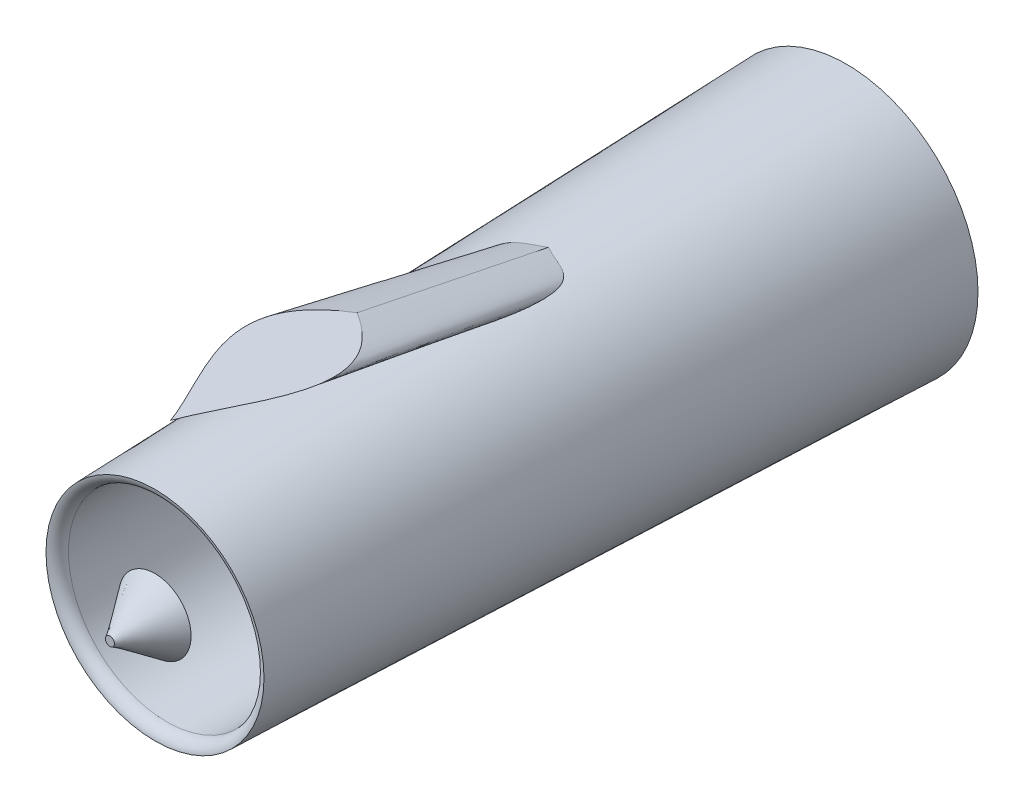
SolidWorks part; units mm, degrees
ref_plane "Front Plane" through (0, 0, 0) normal (0, 0, 1) x (1, 0, 0)
ref_plane "Top Plane" through (0, 0, 0) normal (0, 1, 0) x (1, 0, 0)
ref_plane "Right Plane" through (0, 0, 0) normal (1, 0, 0) x (0, 0, -1)
sketch "Sketch2" plane through (0, 0, 0) normal (0, 1, 0) x (1, 0, 0)
  line L0 (0, -6122.228) -> (0, 2040.7427)
  line L1 (0, 0) -> (-18096.1342, 0) construction
  line L2 (0, 0) -> (-21640.8, -16307.5125) construction
  line L3 (-21640.8, -18450.2946) -> (-21640.8, -15593.2518)
  line L4 (-21640.8, -15593.2518) -> (0, 2040.7427)
  line L5 (-21640.8, -18450.2946) -> (0, -6122.228)
  line L6 (-9083.802, -5361.1886) -> (-9083.802, -6845.1358) construction
  line L7 (-9083.802, -6845.1358) -> (-9083.802, -11296.9774) construction
  line L8 (-9083.802, -6845.1358) -> (0, -6845.1358) construction
  line L9 (0, 408.1485) -> (-18440.4, -13713.752)
  line L10 (0, -35661.6) -> (-7316.724, -42249.6079) construction
  line L11 (0, -35661.6) -> (-8167.6786, -35661.6) construction
  line L12 (0, -34539.0879) -> (0, -39029.1363)
  line L13 (-7316.724, -43428.2455) -> (-7316.724, -41856.7287)
  line L14 (-7316.724, -41856.7287) -> (0, -34539.0879)
  line L15 (0, -39029.1363) -> (-7316.724, -43428.2455)
  line L16 (-2544.3607, -37083.7674) -> (-2544.3607, -37952.5526) construction
  line L17 (-2544.3607, -37952.5526) -> (-2544.3607, -40558.9084) construction
  line L18 (-2544.3607, -37952.5526) -> (0, -37952.5526) construction
  line L19 (-18440.4, -13713.752) -> (-18440.4, -15898.787)
  line L20 (-18440.4, -15898.787) -> (0, -4489.6339)
  line L21 (0, 408.1485) -> (0, -4489.6339) construction
  line L22 (0, -4489.6339) -> (0, 408.1485) construction
  line L23 (0, 408.1485) -> (0, -2040.7427) construction
  line L24 (0, 408.1485) -> (0, -4489.6339) construction
  line L25 (0, -2040.7427) -> (-18440.4, -14806.2695) construction
  line L26 (0, 408.1485) -> (-21640.8, -16164.6603) construction
  line L27 (-6975.7046, -4933.9377) -> (-6975.7046, -6869.7347) construction
  line L28 (-6975.7046, -6869.7347) -> (-6975.7046, -8805.5317) construction
  line L29 (-6975.7046, -6869.7347) -> (0, -6869.7347) construction
  dimension "Wing Sweep" = 37
  dimension "Half Span" = 21640.8
  dimension "Wing Root" = 8162.9707
  dimension "D4" = 2040.7427
  dimension "Wing Tip" = 2857.0428
  dimension "D6" = 714.2607
  dimension "Wing YBar" = 9083.802
  dimension "Tail Sweep" = 42
  dimension "Tail Root" = 4490.0484
  dimension "D10" = 1122.5121
  dimension "Tail Tip" = 1571.5168
  dimension "D12" = 392.8792
  dimension "D13" = 7316.724
  dimension "Tail Ybar" = 2544.3607
  dimension "First Spar" = 1632.5941
  dimension "Second Spar" = 6530.3766
  dimension "Fuel Tip" = 2185.035
  dimension "Tip Spar" = 571.4086
  dimension "Fuel Ybar" = 6975.7046
  dimension "Fuel Tank Length" = 18440.4
  dimension "Tail Arm" = 35661.6
sketch "Sketch4" plane through (0, 0, 0) normal (0, 1, 0) x (1, 0, 0)
  line L0 (0, 17538.8642) -> (0, -40677.9358) construction
  line L1 (-2194.56, 17538.8642) -> (2194.56, 17538.8642) construction
  line L2 (-2194.56, 10955.1842) -> (-2194.56, -31899.6958)
  line L3 (-2194.56, -40677.9358) -> (2194.56, -40677.9358) construction
  line L4 (2194.56, 10955.1842) -> (2194.56, -31899.6958)
  line L5 (0, -6122.228) -> (0, 2040.7427) construction
  line L6 (-9083.802, -6845.1358) -> (0, -6845.1358) construction
  line L7 (-2544.3607, -37952.5526) -> (0, -37952.5526) construction
  line L8 (0, 0) -> (-21640.8, -16307.5125) construction
  line L9 (-21640.8, -15593.2518) -> (0, 2040.7427) construction
  line L10 (-8474.964, 1555.5245) -> (-5807.964, 1555.5245)
  line L11 (-8474.964, 1555.5245) -> (-8474.964, -5453.2245)
  line L12 (-8474.964, -5453.2245) -> (-5807.964, -5453.2245)
  line L13 (-5807.964, 1555.5245) -> (-5807.964, -5453.2245)
  line L14 (2194.56, 10955.1842) -> (-2194.56, 10955.1842)
  arc A0 (-2194.56, -31899.6958) -> (2194.56, -31899.6958) centre (0, -31899.6958) ccw construction
  spline S0 degree 2 poles (-2194.56, 10955.1842) (-2319.3121, 14550.827) (0, 17538.8642) knots 0 0 0 1 1 1 construction
  spline S1 degree 2 poles (2194.56, 10955.1842) (2319.3121, 14550.827) (0, 17538.8642) knots 0 0 0 1 1 1 construction
  spline S2 degree 3 poles (-2194.56, -31899.6958) (-2185.0252, -17343.0176) (-1882.3736, -55849.4008) (-475.0937, -22625.7195) (0, -39029.1363) knots 0 0 0 0 0.566127 1 1 1 1 construction
  spline S3 degree 3 poles (2194.56, -31899.6958) (2185.0252, -17343.0176) (1882.3736, -55849.4008) (475.0937, -22625.7195) (0, -39029.1363) knots 0 0 0 0 0.566127 1 1 1 1 construction
  spline S4 degree 2 poles (-2194.56, -31899.6958) (-4104.2514, -24790.3016) (0, -27753.3552) knots 0 0 0 1 1 1
  spline S5 degree 2 poles (2194.56, -31899.6958) (4104.2514, -24790.3016) (0, -27753.3552) knots 0 0 0 1 1 1
  point P6 (0, 10955.1842)
  point P7 (0, -31899.6958)
  point P8 (0, -6845.1358)
  point P15 (0, -34094.2558)
  point P28 (-7141.464, 1555.5245)
  point P29 (-7141.464, -3778.4755)
  point P35 (-7141.464, -5381.4791)
  point P44 (-7141.464, -1247.9751)
  dimension "Fuse Length" = 58216.8
  dimension "Fuse Dia" = 4389.12
  dimension "D3" = 6583.68
  dimension "D4" = 8778.24
  dimension "D6" = 7141.464
  dimension "Engine Dia" = 2667
  dimension "Engine Length" = 7008.749
  dimension "D9" = 5334
  dimension "D10" = 2803.4996
  dimension "D11" = 5597.1607
  dimension "D2" = 24384
ref_plane "Plane1" through (0, 609.6, 0) normal (0, 1, 0) x (1, 0, 0)
sketch "Sketch10" plane through (0, 0, 0) normal (0, 1, 0) x (1, 0, 0)
  line L0 (-21640.8, -15593.2518) -> (-2194.56, 252.5066)
  line L1 (-2194.56, 10955.1842) -> (-2194.56, -31899.6958) construction
  line L2 (-21640.8, -15593.2518) -> (-21640.8, -18450.2946)
  line L3 (-21640.8, -18450.2946) -> (-7141.464, -10190.49)
  line L4 (-7141.464, -10190.49) -> (-2194.56, -10190.49)
  line L5 (-21640.8, -18450.2946) -> (0, -6122.228) construction
  line L6 (-21640.8, -15593.2518) -> (0, 2040.7427) construction
  line L7 (-2194.56, -10190.49) -> (-2194.56, 252.5066) construction
  line L9 (0, 271.2873) -> (0, -10190.49)
  line L10 (0, -10190.49) -> (-2194.56, -10190.49)
  line L11 (0, -6122.228) -> (0, 2040.7427) construction
  line L12 (-2194.56, 252.5066) -> (0, 2040.7427)
  line L13 (0, 2040.7427) -> (0, 271.2873)
ref_plane "Plane4" through (17269.5438, 0, 17267.3802) normal (0.7072, 0, 0.7071) x (0.7071, 0, -0.7072)
ref_plane "Plane2" through (-7316.724, 0, 0) normal (1, 0, 0) x (0, 0, -1)
ref_plane "Plane5" through (0, 0, -1555.5245) normal (0, 0, 1) x (1, 0, 0)
ref_plane "Plane6" through (0, 0, 5453.2245) normal (0, 0, 1) x (1, 0, 0)
ref_plane "Plane7" through (-7141.464, 0, 0) normal (1, 0, 0) x (0, 0, -1)
sketch "Sketch13" plane through (0, 0, -1555.5245) normal (0, 0, 1) x (1, 0, 0)
  line L1 (-8474.964, 0) -> (-5807.964, 0) construction
  line L2 (-7141.464, 0) -> (-5807.964, 0) construction
  line L3 (-7141.464, 0) -> (-7141.464, -1333.5) construction
  circle A0 centre (-7141.464, 0) radius 1333.5
sketch "Sketch14" plane through (0, 0, 5453.2245) normal (0, 0, 1) x (1, 0, 0)
  line L0 (-8474.964, 0) -> (-5807.964, 0) construction
  line L1 (-7141.464, 0) -> (-6036.564, 0) construction
  line L2 (-7141.464, 0) -> (-7141.464, -1104.9) construction
  line L3 (-7141.464, 0) -> (-7269.5435, 1097.4514) construction
  circle A0 centre (-7141.464, 0) radius 1104.9
  point P2 (-7199.6587, 1103.3664)
  dimension "D1" = 228.6
sketch "Sketch15" plane through (-7141.464, 0, 0) normal (1, 0, 0) x (0, 0, -1)
  line L0 (1555.5245, 0) -> (-5453.2245, 0) construction
  line L1 (1555.5245, 0) -> (-5453.2245, 0) construction
  line L2 (1555.5245, 0) -> (1555.5245, -1333.5) construction
  line L3 (-5453.2245, 0) -> (-5453.2245, -1104.9) construction
  line L6 (1555.5245, -1333.5) -> (-5453.2245, -1104.9) construction
  line L7 (1555.5245, -1333.5) -> (-5492.1559, -1333.5) construction
  spline S0 degree 2 poles (1555.5245, -1333.5) (-1952.2418, -1373.4011) (-5453.2245, -1104.9) knots 0 0 0 1 1 1
loft "Loft2" add profiles "Sketch13", "Sketch14" connector at (-5807.964, 0, -1555.5245) connector at (-6036.564, 0, 5453.2245)
sketch "Sketch16" plane through (0, 0, -1555.5245) normal (0, 0, -1) x (-1, 0, 0)
  circle A0 centre (7141.464, 0) radius 998.22
  circle A1 centre (7141.464, 0) radius 1333.5 construction
  circle A2 centre (7141.464, 0) radius 1104.9 construction
  dimension "D1" = 106.68
extrude "Cut-Extrude1" cut sketch "Sketch16" against normal through all both and the other way through all
fillet "Fillet1" radius 304.8 1 edges at (-6143.244, 0, -1555.5245)
fillet "Fillet2" radius 121.92 1 edges at (-6143.244, 0, 5453.2245)
ref_plane "Plane8" through (0, 1097.4514, 0) normal (0, 1, 0) x (1, 0, 0)
sketch "Sketch17" plane through (0, 1097.4514, 0) normal (0, 1, 0) x (1, 0, 0)
  line L0 (-7141.464, 1555.5245) -> (-7141.464, -5453.2245) construction
  line L1 (-8474.964, 1555.5245) -> (-5807.964, 1555.5245) construction
  line L2 (-8474.964, -5453.2245) -> (-5807.964, -5453.2245) construction
  spline S0 degree 3 poles (-7141.464, -790.7751) (-6485.1332, -1204.5057) (-6910.3771, -2338.0774) (-7141.464, -2877.7155) knots 0 0 0 0 1 1 1 1
  spline S1 degree 3 poles (-7141.464, -790.7751) (-7797.7948, -1204.5057) (-7372.5509, -2338.0774) (-7141.464, -2877.7155) knots 0 0 0 0 1 1 1 1
  dimension "D1" = 457.2
sketch "Sketch18" plane through (0, 0, 5453.2245) normal (0, 0, 1) x (1, 0, 0)
  circle A0 centre (-7141.464, 0) radius 365.76
  dimension "D1" = 731.52
ref_plane "Plane9" through (0, 0, 5910.4245) normal (0, 0, 1) x (1, 0, 0)
sketch "Sketch19" plane through (0, 0, 5910.4245) normal (0, 0, 1) x (1, 0, 0)
  circle A0 centre (-7141.464, 0) radius 45.72
  dimension "D1" = 91.44
loft "Loft3" add profiles "Sketch19", "Sketch18" connector at (-7186.5469, 7.6058, 5910.4245) connector at (-7375.669, 280.942, 5453.2245)
ref_plane "Plane10" through (0, 1630.8514, 0) normal (0, 1, 0) x (1, 0, 0)
sketch "Sketch20" plane through (0, 1630.8514, 0) normal (0, 1, 0) x (1, 0, 0)
  line L0 (-7141.464, -3406.1504) -> (-7141.464, -5295.5283) construction
  line L1 (-7141.464, 1555.5245) -> (-7141.464, -5453.2245) construction
  spline S0 degree 3 poles (-7141.464, -3406.1504) (-6258.7927, -3941.7134) (-6917.016, -4684.3076) (-7141.464, -5295.5283) knots 0 0 0 0 1 1 1 1
  spline S1 degree 3 poles (-7141.464, -3406.1504) (-8024.1353, -3941.7134) (-7365.912, -4684.3076) (-7141.464, -5295.5283) knots 0 0 0 0 1 1 1 1
loft "Loft4" add profiles "Sketch20", "Sketch17" connector at (-7141.464, 1630.8514, 3406.1504) connector at (-7141.464, 1097.4514, 790.7751)
ref_plane "Plane11" through (0, 1265.0914, 0) normal (0, 1, 0) x (1, 0, 0)
sketch "Sketch21" plane through (0, 1265.0914, 0) normal (0, 1, 0) x (1, 0, 0)
  line L0 (-5807.964, 1555.5245) -> (-5807.964, -5453.2245) construction
  line L1 (-5807.964, 1555.5245) -> (-8474.964, 1555.5245)
  line L2 (-5807.964, 1555.5245) -> (-5807.964, -5453.2245)
  line L3 (-5807.964, -5453.2245) -> (-8474.964, -5453.2245)
  line L4 (-8474.964, 1555.5245) -> (-8474.964, -5453.2245)
  line L5 (-8474.964, 1555.5245) -> (-8474.964, -5453.2245) construction
  line L6 (-8474.964, -5453.2245) -> (-5807.964, -5453.2245) construction
  dimension "D2" = 0
equation "\"D6@Sketch2\" = \"Wing Tip@Sketch2\" / 4"
equation "\"D4@Sketch2\" = \"Wing Root@Sketch2\" / 4"
equation "\"D10@Sketch2\" = \"Tail Root@Sketch2\" / 4"
equation "\"D12@Sketch2\" = \"Tail Tip@Sketch2\" / 4"
equation "\"D13@Sketch2\"=48.01/2"
equation "\"First Spar@Sketch2\"=0.2 * \"Wing Root@Sketch2\""
equation "\"Second Spar@Sketch2\"    = 0.8 * \"Wing Root@Sketch2\""
equation "\"Tip Spar@Sketch2\"=0.2 * \"Wing Tip@Sketch2\""
equation "\"D3@Sketch4\" = 1.5 * \"Fuse Dia@Sketch4\""
equation "\"D4@Sketch4\" = 2 * \"Fuse Dia@Sketch4\""
equation "\"D6@Sketch4\" = 0.33 * \"Half Span@Sketch2\""
equation "\"D9@Sketch4\" = 2 * \"Engine Dia@Sketch4\""
equation "\"D10@Sketch4\" = 0.40 * \"Engine Length@Sketch4\""
